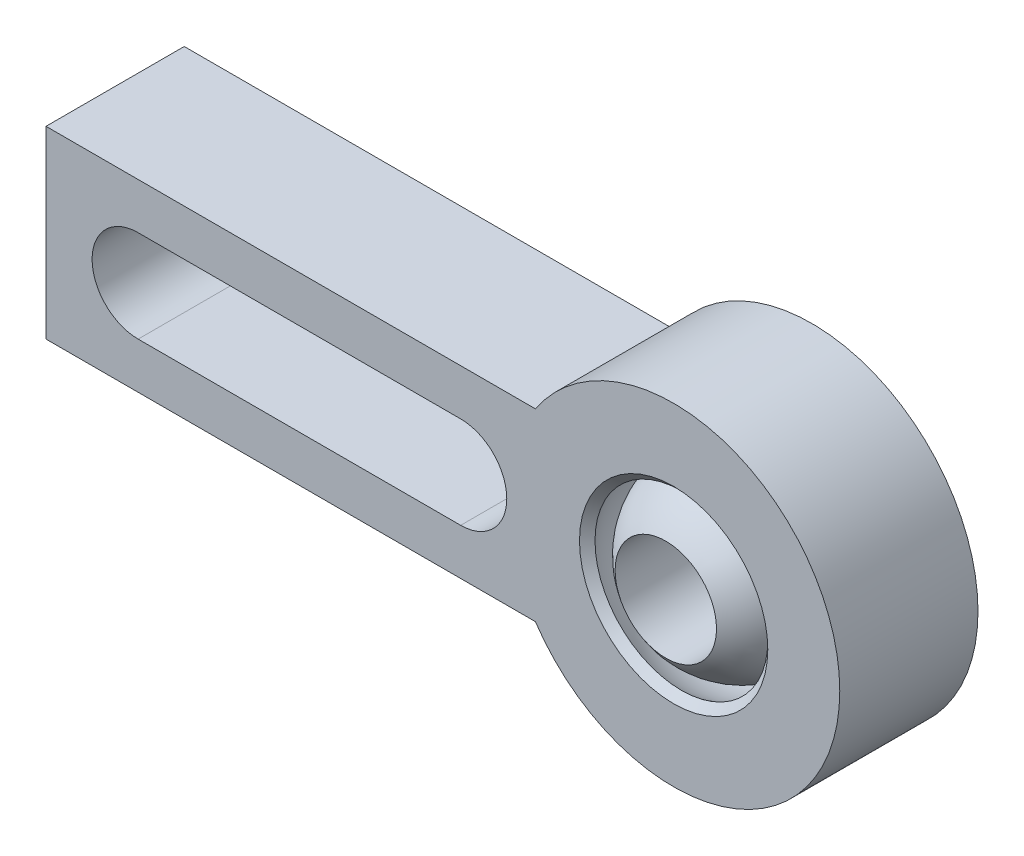
SolidWorks part; units mm, degrees
ref_plane "Front Plane" through (0, 0, 0) normal (0, 0, 1) x (1, 0, 0)
ref_plane "Top Plane" through (0, 0, 0) normal (0, 1, 0) x (1, 0, 0)
ref_plane "Right Plane" through (0, 0, 0) normal (1, 0, 0) x (0, 0, -1)
sketch "Sketch1" plane through (0, 0, 0) normal (0, 0, 1) x (1, 0, 0)
  line L4 (2.4014, 9.6997) -> (2.4014, -0.4603) construction
  line L6 (-24.5786, 9.6997) -> (-24.5786, -0.4603)
  line L7 (10.0214, 10.4617) -> (10.0214, -1.2223)
  line L10 (2.4014, 9.6997) -> (-24.5786, 9.6997)
  line L12 (2.4014, -0.4603) -> (-24.5786, -0.4603)
  line L17 (-11.0886, 9.6997) -> (-11.0886, -0.4603) construction
  line L20 (-19.4986, 4.6197) -> (-1.7186, 4.6197) construction
  line L21 (-19.4986, 7.1597) -> (-1.7186, 7.1597)
  line L22 (-19.4986, 2.0797) -> (-1.7186, 2.0797)
  arc A0 (2.4014, 9.6997) -> (2.4014, -0.4603) centre (10.0214, 4.6197) cw
  arc A3 (10.0214, 9.6997) -> (10.0214, -0.4603) centre (10.0214, 4.6197) ccw
  arc A4 (10.0214, 10.4617) -> (10.0214, -1.2223) centre (10.0214, 4.6197) ccw
  circle A5 centre (10.0214, 4.6197) radius 2.794
  arc A6 (-19.4986, 7.1597) -> (-19.4986, 2.0797) centre (-19.4986, 4.6197) ccw
  arc A7 (-1.7186, 2.0797) -> (-1.7186, 7.1597) centre (-1.7186, 4.6197) ccw
  point P14 (-12.6328, 6.0507)
  point P15 (-10.6086, 4.6197)
  point P20 (10.0214, 9.6962)
  point P21 (10.0214, -0.4408)
  point P22 (10.0214, 4.6197)
  dimension "D4" = 0.762
  dimension "D5" = 5.08
  dimension "D6" = 5.588
  dimension "D7" = 17.78
  dimension "D8" = 5.08
  dimension "D1" = 5.08
  dimension "D3" = 7.62
  dimension "D9" = 10.16
extrude "Boss-Extrude2" add sketch "Sketch1" along normal mid plane 7.62 separate body contours A0 | A0 L12 L6 L10 | L22 A7 L21 A6 region at (-11.0886, 9.2254, 0)
revolve "Cut-Revolve9" cut sketch "Sketch1<11>" angle 360 about L7
sketch "Sketch1<11>" plane through (0, 0, 0) normal (0, 0, 1) x (1, 0, 0) same geometry as "Sketch1"
revolve "Revolve7" add sketch "Sketch1<12>" angle 360 about L7 region at (9.9078, 8.5567, 0)
sketch "Sketch1<12>" plane through (0, 0, 0) normal (0, 0, 1) x (1, 0, 0) same geometry as "Sketch1"
extrude "Cut-Extrude1" cut sketch "Sketch1<13>" against normal through all both and the other way through all contours L7 A5 | L7 A5 region at (11.2072, 4.6197, 0) region at (8.8356, 4.6197, 0)
sketch "Sketch1<13>" plane through (0, 0, 0) normal (0, 0, 1) x (1, 0, 0) same geometry as "Sketch1"
chamfer "Chamfer2" distance 0.762 angle 45 2 edges at (14.45, 4.6197, -3.81) (14.45, 4.6197, 3.81) first distance on face at (14.45, 4.6197, 3.81)
